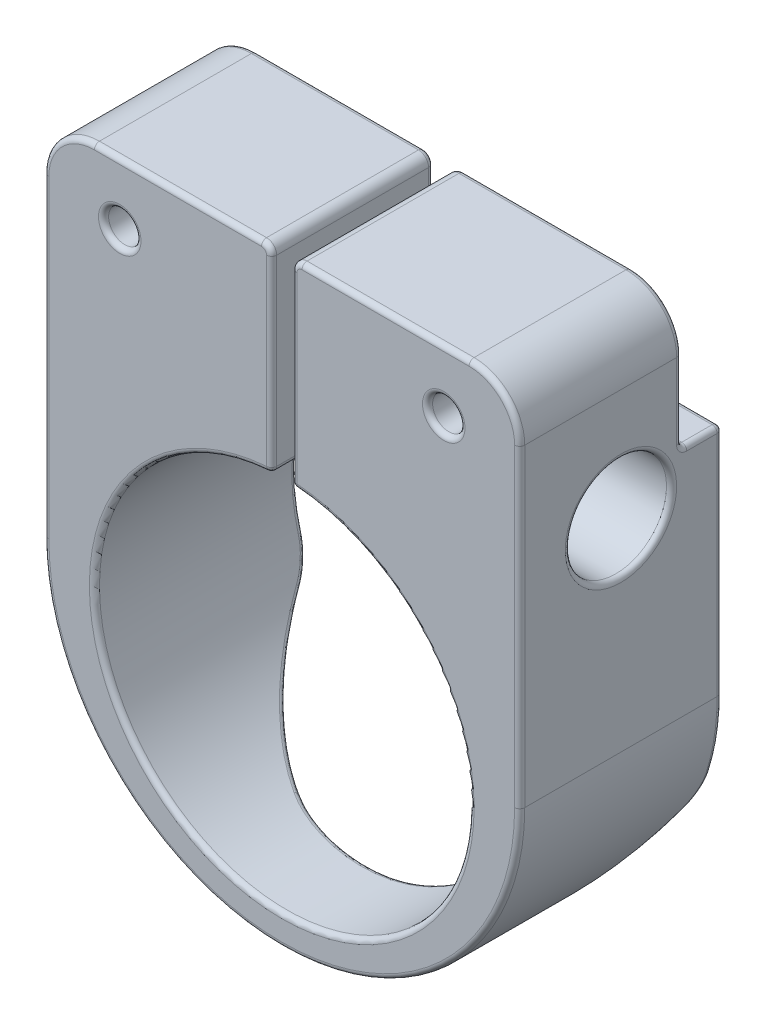
SolidWorks part; units mm, degrees
material "ABS"
ref_plane "Front" through (0, 0, 0) normal (0, 0, 1) x (1, 0, 0)
ref_plane "Top" through (0, 0, 0) normal (0, 1, 0) x (1, 0, 0)
ref_plane "Right" through (0, 0, 0) normal (1, 0, 0) x (0, 0, -1)
sketch "Esquisse1" plane through (0, 0, 0) normal (0, 0, 1) x (1, 0, 0)
  line L1 (-23.5, 38) -> (23.5, 38)
  line L2 (-23.5, 38) -> (-23.5, 2)
  line L4 (23.5, 38) -> (23.5, 2)
  circle A0 centre (0, 0) radius 18.5
  arc A2 (-23.5, 2) -> (23.5, 2) centre (0, 2) ccw
  point P8 (0, 38)
  point P11 (0, -21.5)
  dimension "D1" = 37
  dimension "D2" = 38
  dimension "D4" = 3
  dimension "D3" = 47
extrude "Boss.-Extru.1" add sketch "Esquisse1" along normal blind 20
sketch "Esquisse2" plane through (23.5, 0, 0) normal (1, 0, 0) x (0, 0, -1)
  line L1 (0, 38) -> (-4, 38)
  line L2 (0, 38) -> (0, 25)
  line L3 (0, 25) -> (-4, 25)
  line L4 (-4, 38) -> (-4, 25)
  dimension "D1" = 4
  dimension "D2" = 13
  dimension "D3" = 25
extrude "Enlèv. mat.-Extru.1" cut sketch "Esquisse2" against normal through all
sketch "Esquisse3" plane through (0, 0, 4) normal (0, 0, -1) x (-1, 0, 0)
  line L0 (0, 50) -> (0, -50) construction
  line L1 (23.5, 25) -> (-23.5, 25) construction
  line L2 (23.5, 38) -> (-23.5, 38) construction
  line L3 (-1, 38) -> (1, 38)
  line L4 (-1, 38) -> (-1, 0)
  line L5 (-1, 0) -> (1, 0)
  line L6 (1, 38) -> (1, 0)
  circle A0 centre (-16, 32) radius 1.6
  circle A2 centre (16, 32) radius 1.6
  dimension "D1" = 32
  dimension "D2" = 7
  dimension "D3" = 3.2
  dimension "D4" = 2
extrude "Enlèv. mat.-Extru.2" cut sketch "Esquisse3" against normal through all both and the other way through all
sketch "Esquisse4" plane through (-23.5, 0, 0) normal (-1, 0, 0) x (0, 0, 1)
  line L1 (0, 25) -> (0, 2) construction
  line L2 (20, 38) -> (20, 2) construction
  circle A0 centre (10, 22) radius 1.6
  dimension "D1" = 22
  dimension "D2" = 10
  dimension "D3" = 10
  dimension "D4" = 3.2
extrude "Enlèv. mat.-Extru.3" cut sketch "Esquisse4" against normal through all
sketch "Esquisse5" plane through (-23.5, 0, 0) normal (-1, 0, 0) x (0, 0, 1)
  circle A0 centre (10, 22) radius 5
  dimension "D1" = 10
extrude "Enlèv. mat.-Extru.4" cut sketch "Esquisse5" against normal blind 12
mirror "Symétrie1" about plane through (0, 0, 0) normal (1, 0, 0) of "Enlèv. mat.-Extru.4"
fillet "Congé1" radius 5 2 edges at (-23.5, 38, 12) (23.5, 38, 12)
fillet "Congé2" radius 1 4 edges at (-1, 38, 12) (1, 38, 12) (11.5, 17, 10) (-11.5, 17, 10)
fillet "Congé3" radius 0.5 4 edges at (12.25, 25, 4) (-12.25, 25, 4) (-12.25, 25, 0) (12.25, 25, 0)
sketch "Esquisse7" plane through (-23.5, 0, 0) normal (-1, 0, 0) x (0, 0, 1)
  line L1 (0, -21.5) -> (12, -21.5)
  line L2 (0, -21.5) -> (0, -7)
  line L3 (0, -7) -> (12, -19)
  line L4 (12, -21.5) -> (12, -19)
  dimension "D1" = 12
  dimension "D2" = 19
  dimension "D3" = 45
extrude "Enlèv. mat.-Extru.5" cut sketch "Esquisse7" against normal through all
fillet "Congé4" radius 5 3 edges at (19.4164, -7, 0) (-19.4164, -7, 0) (0, -19, 12)
fillet "Congé5" radius 0.5 62 edges at (15.0189, 10.802, 0) (17.2656, -6.6444, 0.3035) (12.0582, -14.0303, 7.0303) (2.1467, -18.375, 11.2109) (-12.0582, -14.0303, 7.0303) (-17.1243, -7.0007, 0.4494) (1, 27.7365, 20) (1.2929, 37.7071, 20) (10.25, 38, 20) (22.0355, 36.5355, 20) (23.5, 17.5, 20) (0, -21.5, 20) (-23.5, 17.5, 20) (-22.0355, 36.5355, 20) (-10.25, 38, 20) (-1.2929, 37.7071, 20) (1, 21.4865, 0) (1, 24.8536, 0.1464) (1, 25, 2) (1, 25.1464, 3.8536) (1, 31.25, 4) (1.2929, 37.7071, 4) (10.25, 38, 4) (22.0355, 36.5355, 4) (23.5, 29.25, 4) (23.5, 25.1464, 3.8536) (23.5, 25, 2) (23.5, 24.8536, 0.1464) (23.5, 13.25, 0) (23.2374, -1.5036, 0) (21.7089, -6.9986, 0.4485) (17.6446, -13.5216, 6.5216) (10.9059, -18.8161, 11.4626) (0, -21.5, 12) (-11.0307, -18.7503, 11.4288) (-17.6446, -13.5216, 6.5216) (-21.8437, -6.6662, 0.3115) (-23.2374, -1.5036, 0) (-23.5, 13.25, 0) (-23.5, 24.8536, 0.1464) (-23.5, 25, 2) (-23.5, 25.1464, 3.8536) (-23.5, 29.25, 4) (-22.0355, 36.5355, 4) (-10.25, 38, 4) (-1.2929, 37.7071, 4) (-1, 31.25, 4) (-1, 25.1464, 3.8536) (-1, 25, 2) (-1, 24.8536, 0.1464) (-1, 18.473, 10) (1, 18.473, 10) (0, -18.5, 20) (-15.0189, 10.802, 0) (-1, 27.7365, 20) (-1, 21.4865, 0) (-23.5, 17, 10) (23.5, 17, 10) (16, 30.4, 4) (16, 33.6, 20) (-16, 30.4, 4) (-16, 30.4, 20)
